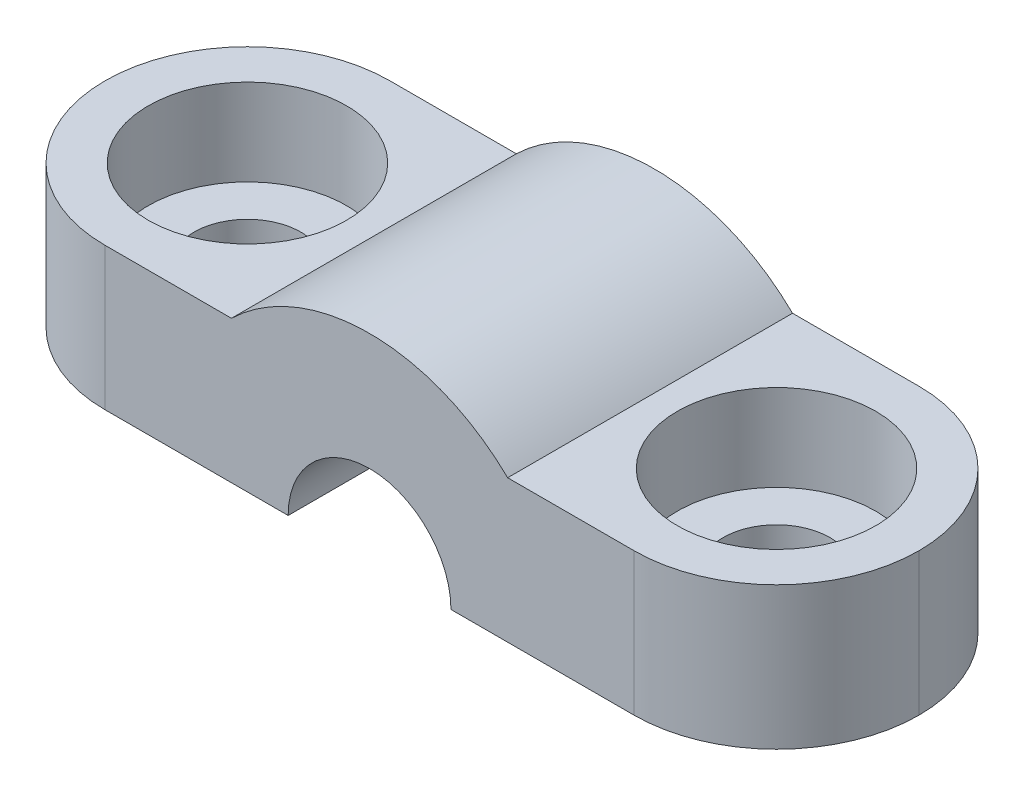
SolidWorks part; units mm, degrees
material "ABS"
ref_plane "Front Plane" through (0, 0, 0) normal (0, 0, 1) x (1, 0, 0)
ref_plane "Top Plane" through (0, 0, 0) normal (0, 1, 0) x (1, 0, 0)
ref_plane "Right Plane" through (0, 0, 0) normal (1, 0, 0) x (0, 0, -1)
ref_axis "Axis1" through (0, 0, 0) along (0, 0, 1)
sketch "Sketch1" plane through (0, 0, 0) normal (0, 1, 0) x (1, 0, 0)
  line L1 (-20, 7) -> (20, 7)
  line L2 (-20, 7) -> (-20, -7)
  line L3 (-20, -7) -> (20, -7)
  line L4 (20, 7) -> (20, -7)
  line L5 (-20, 7) -> (20, -7) construction
  line L6 (-20, -7) -> (20, 7) construction
  point P0 (0, 0)
  dimension "D1" = 14
  dimension "D2" = 40
extrude "Boss-Extrude1" add sketch "Sketch1" along normal blind 7
fillet "Fillet1" radius 7 4 edges at (-20, 3.5, 7) (20, 3.5, 7) (20, 3.5, -7) (-20, 3.5, -7)
sketch "Sketch2" plane through (0, 7, 0) normal (0, 1, 0) x (1, 0, 0)
  line L0 (0, 0) -> (0, 10.3236) construction
  circle A0 centre (-13, 0) radius 2.625
  circle A1 centre (13, 0) radius 2.625
  dimension "D1" = 5.25
extrude "Cut-Extrude1" cut sketch "Sketch2" against normal through all
sketch "Sketch3" plane through (0, 7, 0) normal (0, 1, 0) x (1, 0, 0)
  line L0 (0, 0) -> (0, 13.794) construction
  circle A0 centre (-13, 0) radius 4.875
  circle A1 centre (13, 0) radius 4.875
  dimension "D1" = 9.75
extrude "Cut-Extrude2" cut sketch "Sketch3" against normal blind 4.25
sketch "Sketch4" plane through (0, 0, 7) normal (0, 0, 1) x (1, 0, 0)
  line L0 (-13, 7) -> (13, 7) construction
  line L5 (13, 7) -> (-13, 7)
  line L6 (-13, 7) -> (-13, 0)
  line L7 (-13, 0) -> (13, 0)
  line L8 (13, 0) -> (13, 7)
  line L9 (6.7869, 7) -> (-6.7869, 7)
  arc A0 (6.7869, 7) -> (-6.7869, 7) centre (0, 0) ccw
  dimension "D1" = 9.75
  dimension "D2" = 0
extrude "Boss-Extrude2" add sketch "Sketch4" against normal up to surface (14 mm away) up to face at (0, 3.5, -7)
sketch "Sketch5" plane through (0, 0, 7) normal (0, 0, 1) x (1, 0, 0)
  line L0 (-13, 0) -> (13, 0) construction
  circle A0 centre (0, 0) radius 4
  dimension "D1" = 8
extrude "Cut-Extrude3" cut sketch "Sketch5" against normal through all
